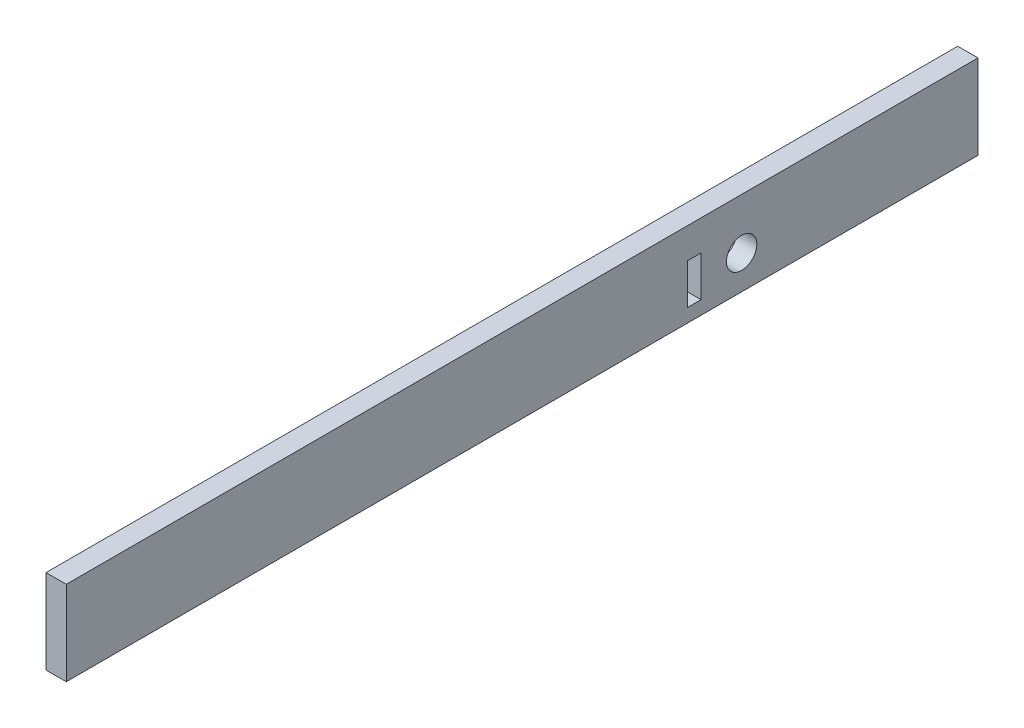
SolidWorks part; units mm, degrees
material "6061-T6 (SS)"
ref_plane "Front Plane" through (0, 0, 0) normal (0, 0, 1) x (1, 0, 0)
ref_plane "Top Plane" through (0, 0, 0) normal (0, 1, 0) x (1, 0, 0)
ref_plane "Right Plane" through (0, 0, 0) normal (1, 0, 0) x (0, 0, -1)
sketch "Sketch1" plane through (0, 0, 0) normal (1, 0, 0) x (0, 0, -1)
  line L0 (200, 10) -> (170.5148, 10) construction
  line L1 (0, 0) -> (270, 0)
  line L2 (0, 0) -> (0, 25)
  line L3 (0, 25) -> (270, 25)
  line L4 (270, 0) -> (270, 25)
  line L5 (184, 16) -> (188, 16)
  line L6 (184, 16) -> (184, 4)
  line L7 (184, 4) -> (188, 4)
  line L8 (188, 16) -> (188, 4)
  circle A0 centre (200, 10) radius 4.5
  point P11 (188, 10)
  dimension "D3" = 9
  dimension "D8" = 12
  dimension "D1" = 270
  dimension "D2" = 25
  dimension "D4" = 10
  dimension "D5" = 70
  dimension "D6" = 4
  dimension "D7" = 12
extrude "Boss-Extrude1" add sketch "Sketch1" along normal blind 6
